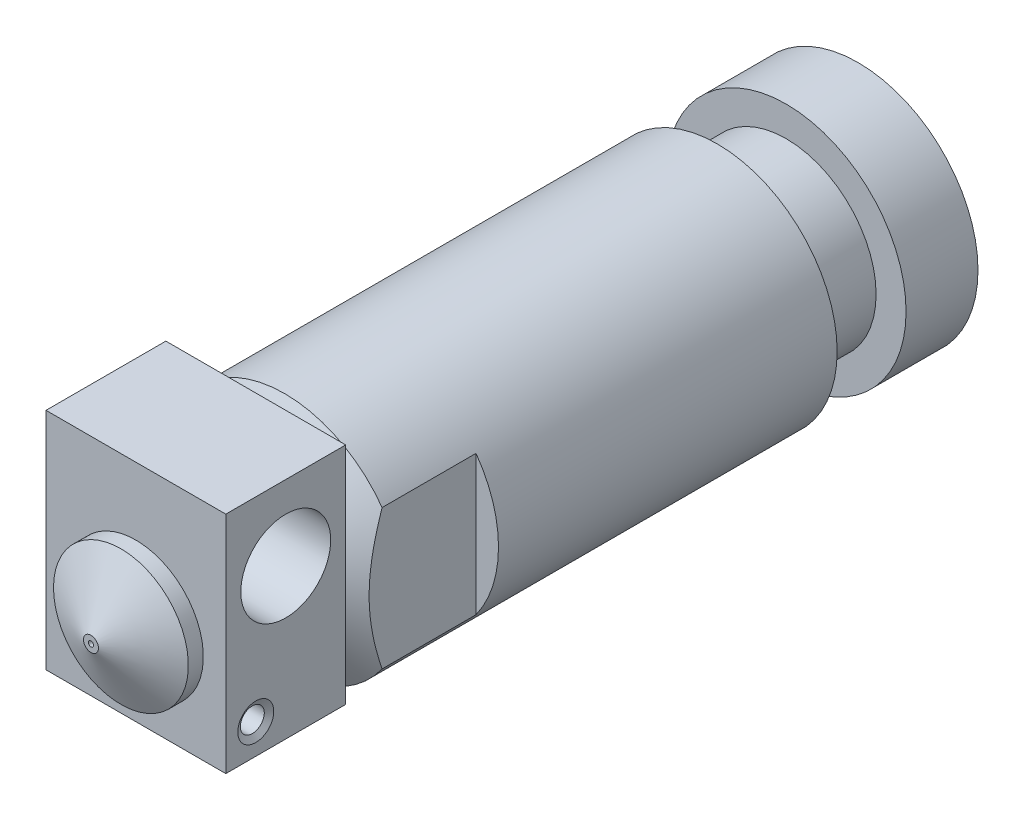
SolidWorks part; units mm, degrees
ref_plane "Plan de face" through (0, 0, 0) normal (0, 0, 1) x (1, 0, 0)
ref_plane "Plan de dessus" through (0, 0, 0) normal (0, 1, 0) x (1, 0, 0)
ref_plane "Plan de droite" through (0, 0, 0) normal (1, 0, 0) x (0, 0, -1)
sketch "Esquisse1" plane through (0, 0, 0) normal (0, 0, 1) x (1, 0, 0)
  circle A0 centre (0, 0) radius 8
  dimension "D1" = 16
extrude "Boss.-Extru.1" add sketch "Esquisse1" along normal blind 40
sketch "Esquisse2" plane through (0, 0, 0) normal (0, 0, -1) x (-1, 0, 0)
  circle A0 centre (0, 0) radius 6
  circle A1 centre (0, 0) radius 8
  dimension "D1" = 12
  dimension "D2" = 16
extrude "Enlèv. mat.-Extru.1" cut sketch "Esquisse2" against normal blind 4.6 from offset 4.8 offset against normal yes
chamfer "Chanfrein1" distance 3 angle 30 1 edges at (8, 0, 40) first distance on face at (8, 0, 40)
sketch "Esquisse3" plane through (0, 0, 40) normal (0, 0, 1) x (1, 0, 0)
  line L1 (-8.5, 6) -> (-6.5, 6)
  line L2 (-8.5, 6) -> (-8.5, -6)
  line L3 (-8.5, -6) -> (-6.5, -6)
  line L4 (-6.5, 6) -> (-6.5, -6)
  line L5 (8.5, 6) -> (6.5, 6)
  line L6 (8.5, 6) -> (8.5, -6)
  line L7 (8.5, -6) -> (6.5, -6)
  line L8 (6.5, 6) -> (6.5, -6)
  dimension "D1" = 13
  dimension "D2" = 6.5
  dimension "D3" = 6
  dimension "D4" = 6
  dimension "D5" = 6
  dimension "D6" = 6
  dimension "D7" = 2
  dimension "D8" = 2
extrude "Enlèv. mat.-Extru.2" cut sketch "Esquisse3" against normal blind 8
sketch "Esquisse4" plane through (0, 0, 0) normal (0, 1, 0) x (1, 0, 0)
  line L0 (-5, -40) -> (5, -40) construction
  line L1 (-8, -9.4) -> (-8, -32) construction
  line L2 (0, 7.1809) -> (0, -45.3206) construction
  circle A0 centre (-5, -26.5) radius 1
  circle A1 centre (-5, -23.5) radius 1
  circle A2 centre (-5, -20.5) radius 1
  circle A3 centre (-5, -17.5) radius 1
  circle A4 centre (-5, -14.5) radius 1
  dimension "D2" = 2
  dimension "D3" = 2
  dimension "D4" = 2
  dimension "D5" = 2
  dimension "D9" = 2
  dimension "D1" = 13.5
  dimension "D6" = 3
  dimension "D7" = 3
  dimension "D8" = 3
  dimension "D10" = 3
  dimension "D11" = 3
revolve "Enlèvement de matière-Révolution1" cut sketch "Esquisse4" angle 360 about L2
sketch "Esquisse8" plane through (0, 0, 0) normal (0, 0, -1) x (-1, 0, 0)
  circle A0 centre (0, 0) radius 1
  dimension "D1" = 2
extrude "Enlèv. mat.-Extru.4" cut sketch "Esquisse8" against normal through all
sketch "Esquisse9" plane through (0, 0, 40) normal (0, 0, 1) x (1, 0, 0)
  circle A0 centre (0, 0) radius 4
  dimension "D1" = 8
extrude "Boss.-Extru.2" add sketch "Esquisse9" along normal blind 0.2
sketch "Esquisse10" plane through (0, 0, 40.2) normal (0, 0, 1) x (1, 0, 0)
  line L1 (6, 9) -> (-6, 9)
  line L2 (6, 9) -> (6, -6)
  line L3 (6, -6) -> (-6, -6)
  line L4 (-6, 9) -> (-6, -6)
  circle A0 centre (0, 0) radius 4 construction
  circle A1 centre (0, 0) radius 4 construction
  dimension "D3" = 6
  dimension "D1" = 15
  dimension "D2" = 12
  dimension "D4" = 6
extrude "Boss.-Extru.3" add sketch "Esquisse10" along normal blind 8
sketch "Esquisse11" plane through (6, 0, 0) normal (1, 0, 0) x (0, 0, -1)
  line L0 (-48.2, -6) -> (-48.2, 9) construction
  line L1 (-48.2, 9) -> (-40.2, 9) construction
  line L2 (-48.2, -6) -> (-40.2, -6) construction
  circle A0 centre (-44.2, 4) radius 3
  circle A1 centre (-46.2, -4) radius 0.7
  dimension "D1" = 6
  dimension "D4" = 1.4
  dimension "D2" = 4
  dimension "D3" = 5
  dimension "D5" = 2
  dimension "D6" = 2
extrude "Enlèv. mat.-Extru.5" cut sketch "Esquisse11" against normal through all contours A0 region at (6, 4, 44.2)
sketch "Esquisse13" plane through (6, 0, 0) normal (1, 0, 0) x (0, 0, -1)
  line L0 (-48.2, -6) -> (-48.2, 9) construction
  line L1 (-48.2, -6) -> (-40.2, -6) construction
  circle A0 centre (-46.2, -4) radius 0.8
  point P4 (-44.2, -6)
  dimension "D1" = 1.6
  dimension "D2" = 2
  dimension "D3" = 2
extrude "Enlèv. mat.-Extru.6" cut sketch "Esquisse13" against normal blind 3
chamfer "Chanfrein2" distance 0.4 angle 30 1 edges at (6, -3.2, 46.2) first distance on face at (6, -3.2, 46.2)
sketch "Esquisse14" plane through (0, 0, 48.2) normal (0, 0, 1) x (1, 0, 0)
  circle A0 centre (0, 0) radius 4.5
  dimension "D1" = 9
  dimension "D2" = 0
extrude "Boss.-Extru.4" add sketch "Esquisse14" along normal blind 1
sketch "Esquisse15" plane through (0, 0, 49.2) normal (0, 0, 1) x (1, 0, 0)
  circle A0 centre (0, 0) radius 4.5
extrude "Boss.-Extru.5" add sketch "Esquisse15" along normal blind 2
chamfer "Chanfrein3" distance 2 distance2 4 1 edges at (4.5, 0, 51.2) first distance on face at (-4.5, 0, 48.2)
sketch "Esquisse16" plane through (0, 0, 51.2) normal (0, 0, 1) x (1, 0, 0)
  circle A0 centre (0, 0) radius 0.175
  dimension "D1" = 0.35
extrude "Enlèv. mat.-Extru.7" cut sketch "Esquisse16" against normal through all
